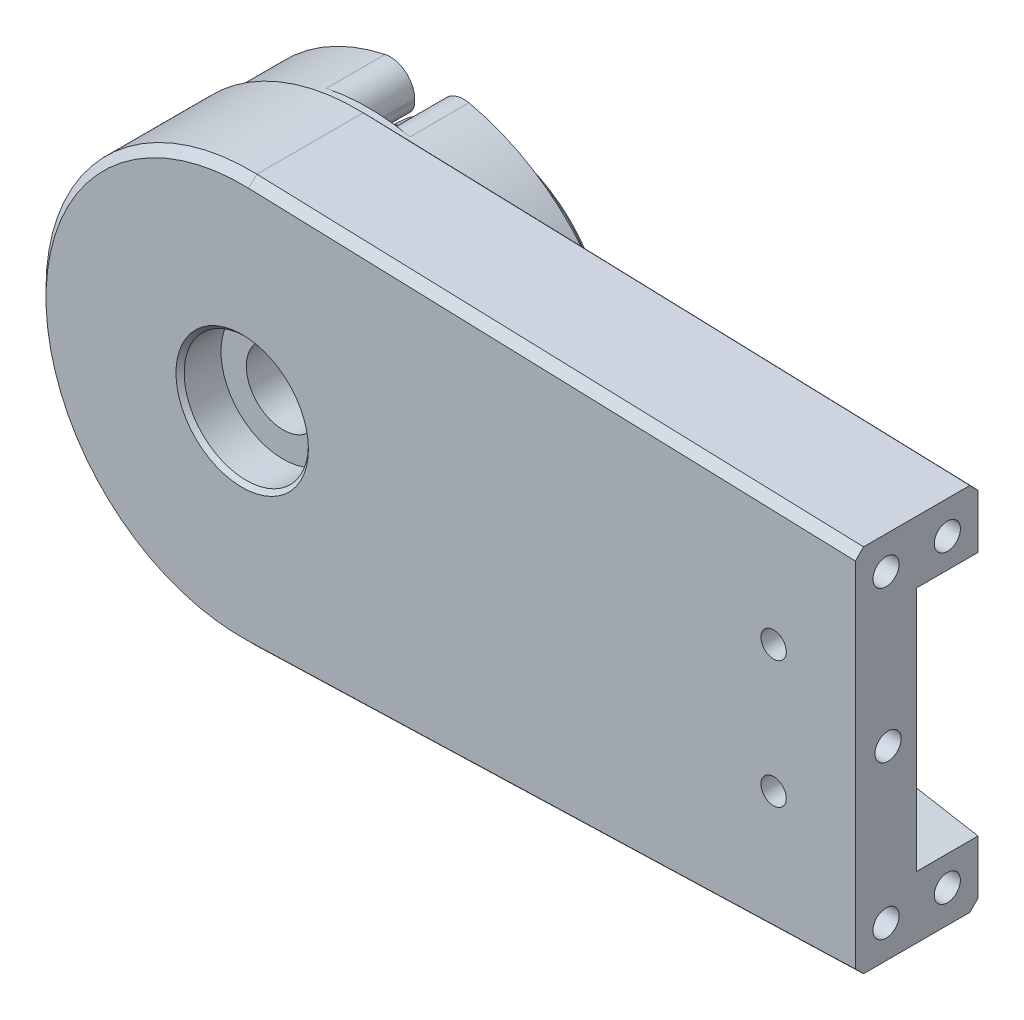
SolidWorks part; units mm, degrees
ref_plane "前视基准面" through (0, 0, 0) normal (0, 0, 1) x (1, 0, 0)
ref_plane "上视基准面" through (0, 0, 0) normal (0, 1, 0) x (1, 0, 0)
ref_plane "右视基准面" through (0, 0, 0) normal (1, 0, 0) x (0, 0, -1)
sketch "旋转草图同步带轮01" plane through (0, 0, 0) normal (1, 0, 0) x (0, 0, -1)
  line L0 (0, 0) -> (1, 0) construction
  line L1 (3, 0) -> (3, 25.2743)
  line L2 (3, 25.2743) -> (-3, 25.2743)
  line L3 (-3, 25.2743) -> (-3, 0)
  line L4 (-3, 0) -> (3, 0)
  dimension "GearBeltOutsideDiameter" = 25.2743
revolve "同步带轮01" add sketch "旋转草图同步带轮01" angle 360 about L0
sketch "齿草图同步带轮01" plane through (0, 0, 0) normal (0, 0, 1) x (1, 0, 0)
  line L0 (-0.8127, 25.2612) -> (0, 27.8143)
  line L1 (0, 27.8143) -> (0.8127, 25.2612)
  arc A0 (0.8127, 25.2612) -> (0.6, 25.0553) centre (0.806, 25.0553) ccw
  arc A1 (0.6, 25.0553) -> (-0.6, 25.0553) centre (0, 25.0553) cw
  arc A2 (-0.6, 25.0553) -> (-0.8127, 25.2612) centre (-0.806, 25.0553) ccw
  dimension "GearBeltToothR1" = 0.4121
  dimension "GearBeltToothR2" = 1.2
  dimension "GearBeltToothCapX1" = 0.8127
  dimension "GearBeltToothCapY1" = 2.5531
  dimension "GearBeltToothCapX2" = 0.8127
  dimension "GearBeltToothCapY2" = 2.5531
extrude "齿拉伸切除同步带轮01" cut sketch "齿草图同步带轮01" against normal blind 3 and the other way blind 3
sketch "孔旋转草图" plane through (0, 0, 0) normal (1, 0, 0) x (0, 0, -1)
  line L0 (0, 0) -> (1, 0) construction
  line L1 (-3, 0) -> (3, 0)
  line L2 (3, 0) -> (3, 6.35)
  line L3 (3, 6.35) -> (-3, 6.35)
  line L4 (-3, 6.35) -> (-3, 0)
  dimension "TaperSide1" = 6.35
  dimension "TaperSide2" = 6.35
revolve "孔旋转切除" cut sketch "孔旋转草图" angle 360 about L0
sketch "草图6" plane through (0, 0, -3) normal (0, 0, -1) x (-1, 0, 0)
  circle A0 centre (0, 0) radius 24.4553
  circle A1 centre (0, 0) radius 27.6497
extrude "切除-拉伸2" cut sketch "草图6" against normal blind 10
sketch "草图7" plane through (0, 0, 3) normal (0, 0, 1) x (1, 0, 0)
  circle A1 centre (0, 0) radius 24.4553
  circle A2 centre (0, 0) radius 24.4553
  dimension "D1" = 0
extrude "凸台-拉伸1" add sketch "草图7" along normal blind 2
sketch "草图8" plane through (0, 0, 5) normal (0, 0, 1) x (1, 0, 0)
  line L0 (0, 0) -> (25, 0) construction
  line L1 (0.8, 24.9872) -> (125.672, 20.9892)
  line L2 (125.672, -20.9892) -> (0.8, -24.9872)
  line L3 (104, 0) -> (125, 0) construction
  arc A0 (0.8, 24.9872) -> (0.8, -24.9872) centre (0, 0) ccw
  arc A1 (125.672, -20.9892) -> (125.672, 20.9892) centre (125, 0) ccw
  circle A2 centre (125, 0) radius 5
  dimension "D1" = 50
  dimension "D3" = 42
  dimension "D4" = 10
  dimension "D2" = 125
extrude "凸台-拉伸2" add sketch "草图8" along normal blind 15
sketch "草图9" plane through (0, 0, -3) normal (0, 0, -1) x (-1, 0, 0)
  circle A0 centre (0, 0) radius 6.35
extrude "凸台-拉伸3" add sketch "草图9" against normal up to surface (6 mm away) up to face at (6.35, 0, 3)
sketch "草图11" plane through (0, 0, -3) normal (0, 0, -1) x (-1, 0, 0)
  circle A0 centre (0, 0) radius 14.8
  dimension "D1" = 29.6
extrude "凸台-拉伸4" add sketch "草图11" along normal blind 7
sketch "草图12" plane through (0, 0, -3) normal (0, 0, -1) x (-1, 0, 0)
  circle A0 centre (0, 0) radius 15
  circle A1 centre (0, 0) radius 17.5
  dimension "D1" = 35
extrude "凸台-拉伸5" add sketch "草图12" along normal blind 1
sketch "草图13" plane through (0, 0, -10) normal (0, 0, -1) x (-1, 0, 0)
  circle A0 centre (0, 0) radius 4.5
  dimension "D1" = 9
extrude "切除-拉伸4" cut sketch "草图13" against normal blind 52
sketch "草图14" plane through (0, 0, -10) normal (0, 0, -1) x (-1, 0, 0)
  circle A0 centre (0, 0) radius 6.65
  dimension "D1" = 13.3
extrude "切除-拉伸5" cut sketch "草图14" against normal blind 5
sketch "草图16" plane through (0, 0, 20) normal (0, 0, 1) x (1, 0, 0)
  circle A0 centre (0, 0) radius 6.65
  dimension "D1" = 13.3
extrude "切除-拉伸6" cut sketch "草图16" against normal blind 8
sketch "草图18" plane through (0, 0, 20) normal (0, 0, 1) x (1, 0, 0)
  line L0 (125.672, 20.9892) -> (0.8, 24.9872) construction
  line L1 (75, 22.6116) -> (158.6372, 22.6116)
  line L2 (75, 22.6116) -> (75, -27.0468)
  line L3 (75, -27.0468) -> (158.6372, -27.0468)
  line L4 (158.6372, 22.6116) -> (158.6372, -27.0468)
  arc A0 (125.672, -20.9892) -> (125.672, 20.9892) centre (125, 0) ccw construction
  dimension "D1" = 50
extrude "切除-拉伸9" cut sketch "草图18" against normal blind 26
sketch "草图19" plane through (0, 0, 5) normal (0, 0, -1) x (-1, 0, 0)
  line L0 (-75, -14.6116) -> (-57, -11.4377)
  line L1 (-75, 22.6116) -> (-75, -22.6116) construction
  line L2 (-57, -11.4377) -> (-57, 11.4377)
  line L3 (-57, 11.4377) -> (-75, 14.6116)
  line L4 (-75, 14.6116) -> (-75, -14.6116)
  point P4 (-57, 0)
  dimension "D1" = 8
  dimension "D2" = 8
  dimension "D3" = 80
  dimension "D4" = 80
  dimension "D5" = 18
extrude "切除-拉伸10" cut sketch "草图19" against normal blind 7.5
sketch "草图20" plane through (75, 0, 0) normal (1, 0, 0) x (0, 0, -1)
  line L1 (-5, 22.6116) -> (-5, 14.6116) construction
  line L3 (-20, 22.6116) -> (-20, -22.6116) construction
  line L4 (-5, -14.6116) -> (-5, -22.6116) construction
  circle A0 centre (-8.75, 18.6116) radius 1.6
  circle A1 centre (-16.25, 18.6116) radius 1.6
  circle A2 centre (-8.75, -18.6116) radius 1.6
  circle A3 centre (-16.25, -18.6116) radius 1.6
  circle A4 centre (-16, 0) radius 1.6
  dimension "D1" = 3.2
  dimension "D2" = 3.2
  dimension "D3" = 3.2
  dimension "D5" = 3.2
  dimension "D6" = 3.2
  dimension "D7" = 3.75
  dimension "D8" = 3.75
  dimension "D9" = 3.75
  dimension "D10" = 3.75
extrude "切除-拉伸11" cut sketch "草图20" against normal blind 10
sketch "草图21" plane through (57, 0, 0) normal (1, 0, 0) x (0, 0, -1)
  line L0 (-5, -11.4377) -> (-5, 11.4377) construction
  circle A0 centre (-8.75, 0) radius 1.6
  dimension "D1" = 3.2
  dimension "D2" = 3.75
extrude "切除-拉伸12" cut sketch "草图21" against normal blind 10
sketch "草图22" plane through (0, 0, 12.5) normal (0, 0, -1) x (-1, 0, 0)
  circle A0 centre (-65, 7.7712) radius 1.55
  circle A1 centre (-65, -7.7712) radius 1.55
extrude "切除-拉伸13" cut sketch "草图22" against normal blind 10
sketch "草图23" plane through (0, 0, -3) normal (0, 0, -1) x (-1, 0, 0)
  line L2 (8.7758, 15.2001) -> (9.5, 16.4545)
  line L5 (-8.7758, 15.2001) -> (-9.5, 16.4545)
  line L6 (1.5, 31.5314) -> (-1.5, 31.5314)
  line L9 (-1.5, 20.7063) -> (-1.5, 31.5314)
  line L10 (1.5, 20.7063) -> (1.5, 31.5314)
  arc A19 (5.7481, 18.1096) -> (6.3717, 17.8998) centre (0, 0) cw
  arc A20 (8.8055, 16.8364) -> (9.5, 16.4545) centre (0, 0) cw
  arc A21 (7.3046, 17.5398) -> (7.9075, 17.2763) centre (0, 0) cw
  arc A22 (-4.7874, 18.387) -> (-4.1479, 18.5417) centre (0, 0) cw
  arc A23 (-6.3717, 17.8998) -> (-5.7481, 18.1096) centre (0, 0) cw
  arc A24 (-7.9075, 17.2763) -> (-7.3046, 17.5398) centre (0, 0) cw
  arc A25 (6.3717, 17.8998) -> (7.3046, 17.5398) centre (6.8405, 17.7259) ccw
  arc A26 (7.9075, 17.2763) -> (8.8055, 16.8364) centre (8.3594, 17.0622) ccw
  arc A27 (4.7874, 18.387) -> (5.7481, 18.1096) centre (5.2696, 18.2546) ccw
  arc A28 (3.1667, 18.7343) -> (4.1479, 18.5417) centre (3.6585, 18.6444) ccw
  arc A29 (-7.9075, 17.2763) -> (-8.8055, 16.8364) centre (-8.3594, 17.0622) cw
  arc A30 (-6.3717, 17.8998) -> (-7.3046, 17.5398) centre (-6.8405, 17.7259) cw
  arc A31 (-4.7874, 18.387) -> (-5.7481, 18.1096) centre (-5.2696, 18.2546) cw
  arc A32 (-3.1667, 18.7343) -> (-4.1479, 18.5417) centre (-3.6585, 18.6444) cw
  arc A33 (-1.5, 20.7063) -> (-3.1667, 18.7343) centre (-3.5, 20.7063) cw
  arc A34 (3.1667, 18.7343) -> (1.5, 20.7063) centre (3.5, 20.7063) cw
  arc A35 (4.1479, 18.5417) -> (4.7874, 18.387) centre (0, 0) cw
  arc A36 (-8.7758, 15.2001) -> (8.7758, 15.2001) centre (0, 0) cw
  arc A37 (-9.5, 16.4545) -> (-8.8055, 16.8364) centre (0, 0) cw
  point P30 (0, 0)
chamfer "倒角1" distance 1 angle 45 6 edges at (37.9, 23.7994, 20) (37.9, -23.7994, 20) (-25, 0, 20) (37.9, 23.7994, 5) (37.9, -23.7994, 5) (-25, 0, 5)
sketch "草图25" plane through (0, 0, 5) normal (0, 0, -1) x (-1, 0, 0)
  line L8 (-75.4, 15.0883) -> (-75.4, -15.0883)
  line L9 (-75.4, -15.0883) -> (-56.6, -11.7733)
  line L10 (-56.6, -11.7733) -> (-56.6, 11.7733)
  line L11 (-56.6, 11.7733) -> (-75.4, 15.0883)
  line L12 (-75.4, 15.0883) -> (-75.4, -15.0883)
  line L13 (-75.4, -15.0883) -> (-56.6, -11.7733)
  line L14 (-56.6, -11.7733) -> (-56.6, 11.7733)
  line L15 (-56.6, 11.7733) -> (-75.4, 15.0883)
  dimension "D1" = 0.4
extrude "切除-拉伸15" cut sketch "草图25" against normal up to surface (7.5 mm away) up to face at (63.45, -7.7712, 12.5)
sketch "草图26" plane through (0, 0, -10) normal (0, 0, -1) x (-1, 0, 0)
  circle A0 centre (0, 0) radius 7.6
extrude "切除-拉伸16" cut sketch "草图26" against normal blind 5
sketch "草图27" plane through (0, 0, 20) normal (0, 0, 1) x (1, 0, 0)
  circle A0 centre (0, 0) radius 7.6
extrude "切除-拉伸17" cut sketch "草图27" against normal blind 5
sketch "草图28" plane through (0, 0, 12) normal (0, 0, 1) x (1, 0, 0)
  circle A0 centre (0, 0) radius 4.5
  circle A1 centre (0, 0) radius 6.65
extrude "凸台-拉伸6" add sketch "草图28" along normal blind 3
sketch "草图30" plane through (0, 0, -3) normal (0, 0, -1) x (-1, 0, 0)
  circle A0 centre (0, 0) radius 14.8
  circle A1 centre (0, 0) radius 15
extrude "凸台-拉伸7" add sketch "草图30" along normal blind 7
sketch "草图31" plane through (0, 0, -10) normal (0, 0, -1) x (-1, 0, 0)
  circle A0 centre (0, 0) radius 15
  circle A1 centre (0, 0) radius 14.9
extrude "切除-拉伸18" cut sketch "草图31" against normal blind 6
chamfer "倒角2" distance 0.5 angle 45 1 edges at (-14.9, 0, -10)
sketch "草图32" plane through (0, 0, -4) normal (0, 0, -1) x (-1, 0, 0)
  circle A0 centre (0, 0) radius 17.5
  circle A1 centre (0, 0) radius 14.9
extrude "切除-拉伸19" cut sketch "草图32" against normal blind 1
sketch "草图33" plane through (0, 0, -3) normal (0, 0, -1) x (-1, 0, 0)
  circle A0 centre (0, 0) radius 17
  circle A1 centre (0, 0) radius 24.4553
extrude "切除-拉伸20" cut sketch "草图33" against normal blind 0.4
chamfer "倒角3" distance 0.5 angle 45 1 edges at (7.6, 0, 20)
chamfer "倒角4" distance 0.5 angle 45 1 edges at (-7.6, 0, -10)
extrude "切除-拉伸22" cut sketch "草图23" against normal blind 7.6
fillet "圆角1" radius 3 2 edges at (-1.5, 24.4092, 1) (1.5, 24.4092, 1)
